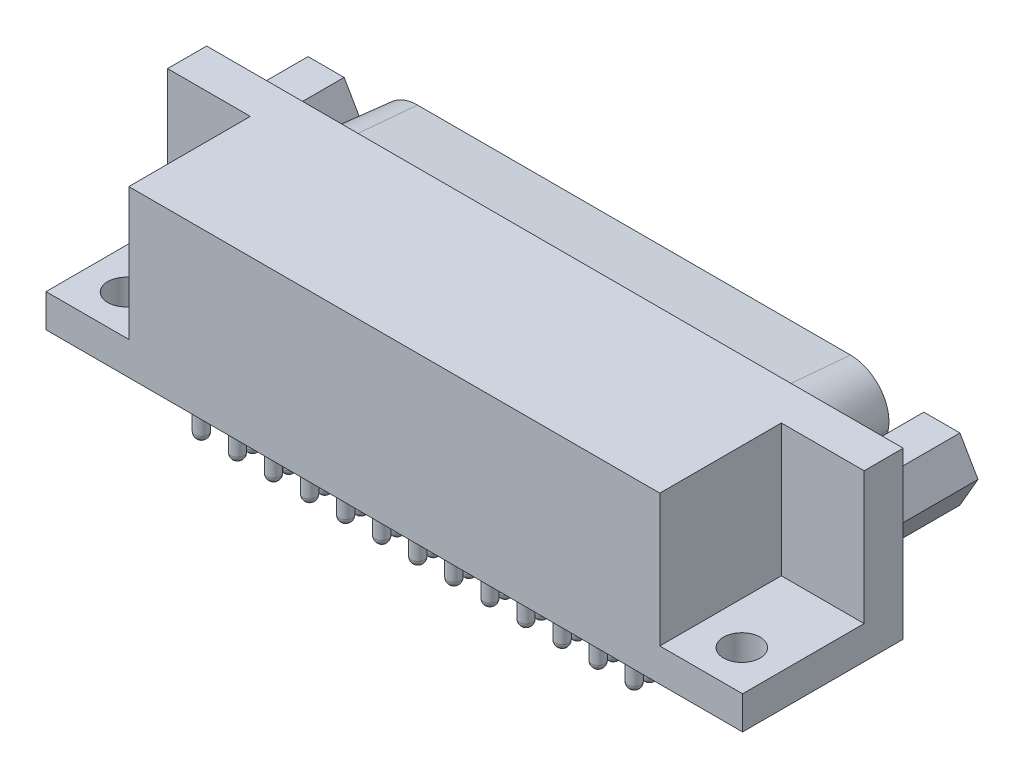
SolidWorks part; units mm, degrees
ref_plane "x/y" through (0, 0, 0) normal (0, 0, 1) x (1, 0, 0)
ref_plane "x/z" through (0, 0, 0) normal (0, 1, 0) x (1, 0, 0)
ref_plane "y/z" through (0, 0, 0) normal (1, 0, 0) x (0, 0, -1)
sketch "Sketch1" plane through (0, 0, 0) normal (0, 1, 0) x (1, 0, 0)
  line L1 (-10.16, -1.77) -> (43.31, -1.77)
  line L2 (-10.16, -1.77) -> (-10.16, 10.56)
  line L3 (-10.16, 10.56) -> (43.31, 10.56)
  line L4 (43.31, -1.77) -> (43.31, 10.56)
  point P3 (16.575, 10.56)
  dimension "D1" = 53.47
  dimension "D2" = 12.33
  dimension "D3" = 1.77
  dimension "D4" = 10.16
extrude "Base-Extrude" add sketch "Sketch1" along normal blind 12.7
sketch "Sketch2" plane through (0, 0, -10.56) normal (0, 0, -1) x (-1, 0, 0)
  line L0 (-16.575, 12.7) -> (-16.575, -6.5379) construction
  line L1 (-43.31, 12.7) -> (10.16, 12.7) construction
  line L2 (-32.6146, 1.37) -> (-0.5354, 1.37)
  line L3 (2.8812, 4.189) -> (3.4616, 7.189)
  line L4 (0.045, 11.33) -> (-33.195, 11.33)
  line L6 (-36.0312, 4.189) -> (-36.6116, 7.189)
  line L7 (-43.31, 0) -> (10.16, 0) construction
  arc A0 (2.8812, 4.189) -> (-0.5354, 1.37) centre (-0.5354, 4.85) cw
  arc A1 (0.045, 11.33) -> (3.4616, 7.189) centre (0.045, 7.85) cw
  arc A2 (-33.195, 11.33) -> (-36.6116, 7.189) centre (-33.195, 7.85) ccw
  arc A3 (-36.0312, 4.189) -> (-32.6146, 1.37) centre (-32.6146, 4.85) ccw
  point P4 (-16.575, 11.33)
  point P12 (2.3358, 1.37)
  point P21 (-16.575, 1.37)
  dimension "D5" = 3.48
  dimension "D1" = 1.37
  dimension "D2" = 1.37
  dimension "D3" = 100.95
  dimension "D4" = 33.24
extrude "Boss-Extrude1" add sketch "Sketch2" along normal blind 6.07 draft 5
sketch "Sketch13" plane through (0, 0, -16.63) normal (0, 0, -1) x (-1, 0, 0)
  line L8 (1.9671, 4.3658) -> (2.5475, 7.3658)
  line L9 (0.045, 10.3989) -> (-33.195, 10.3989)
  line L10 (-35.6975, 7.3658) -> (-35.1171, 4.3658)
  line L11 (-32.6146, 2.3011) -> (-0.5354, 2.3011)
  line L12 (1.9671, 4.3658) -> (2.5475, 7.3658)
  line L13 (0.045, 10.3989) -> (-33.195, 10.3989)
  line L14 (-35.6975, 7.3658) -> (-35.1171, 4.3658)
  line L15 (-32.6146, 2.3011) -> (-0.5354, 2.3011)
  arc A8 (-0.5354, 2.3011) -> (1.9671, 4.3658) centre (-0.5354, 4.85) ccw
  arc A9 (2.5475, 7.3658) -> (0.045, 10.3989) centre (0.045, 7.85) ccw
  arc A10 (-33.195, 10.3989) -> (-35.6975, 7.3658) centre (-33.195, 7.85) ccw
  arc A11 (-35.1171, 4.3658) -> (-32.6146, 2.3011) centre (-32.6146, 4.85) ccw
  arc A12 (-0.5354, 2.3011) -> (1.9671, 4.3658) centre (-0.5354, 4.85) ccw
  arc A13 (2.5475, 7.3658) -> (0.045, 10.3989) centre (0.045, 7.85) ccw
  arc A14 (-33.195, 10.3989) -> (-35.6975, 7.3658) centre (-33.195, 7.85) ccw
  arc A15 (-35.1171, 4.3658) -> (-32.6146, 2.3011) centre (-32.6146, 4.85) ccw
  dimension "D1" = 0.4
extrude "Cut-Extrude5" cut sketch "Sketch13" against normal up to vertex (6.07 mm away) draft 5 up to point (43.31, 12.7, -10.56) draft outward yes
sketch "Sketch6" plane through (0, 0, 0) normal (0, -1, 0) x (1, 0, 0)
  circle A0 centre (0, 0) radius 0.5
  dimension "D1" = 1
extrude "Boss-Extrude2" add sketch "Sketch6" along normal blind 2.54
dome "Dome3" faces to dome 1 distance 0.5 reverse direction no elliptical dome no face at (0, -2.54, -0.5) parameters "D1"=0.5
pattern_linear "LPattern1" count 13 spacing 2.7686 along (1, 0, 0) of "Dome3", "Boss-Extrude2"
sketch "Sketch7" plane through (0, 0, 0) normal (0, -1, 0) x (1, 0, 0)
  line L1 (-10.16, -10.56) -> (-10.16, 1.77) construction
  circle A0 centre (1.397, -2.54) radius 0.5
  circle A1 centre (0, 0) radius 0.5 construction
  dimension "D2" = 11.557
  dimension "D3" = 2.54
extrude "Boss-Extrude3" add sketch "Sketch7" along normal blind 4
dome "Dome4" faces to dome 1 distance 0.5 reverse direction no elliptical dome no face at (1.397, -4, -3.04) parameters "D1"=0.5
pattern_linear "LPattern4" count 12 spacing 2.7686 along (1, 0, 0) of "Boss-Extrude3", "Dome4"
sketch "Sketch14" plane through (0, 0, -10.56) normal (0, 0, -1) x (-1, 0, 0)
  circle A0 centre (0.045, 7.85) radius 0.5
  arc A1 (2.5475, 7.3658) -> (0.045, 10.3989) centre (0.045, 7.85) ccw construction
  dimension "D1" = 1
extrude "Boss-Extrude5" add sketch "Sketch14" along normal blind 4
dome "Dome1" faces to dome 1 distance 0.5 reverse direction no elliptical dome no face at (-0.545, 7.85, -14.56) parameters "D1"=0.5
pattern_linear "LPattern5" count 13 spacing 2.77 along (1, 0, 0) of "Dome1", "Boss-Extrude5"
sketch "Sketch15" plane through (0, 0, -10.56) normal (0, 0, -1) x (-1, 0, 0)
  line L1 (-2.725, 7.85) -> (0.045, 7.85) construction
  line L3 (-1.34, 7.85) -> (-1.34, 5.31) construction
  circle A0 centre (-1.34, 5.31) radius 0.5
  circle A1 centre (0.045, 7.85) radius 0.5 construction
  circle A2 centre (-2.725, 7.85) radius 0.5 construction
  dimension "D1" = 2.54
extrude "Boss-Extrude6" add sketch "Sketch15" along normal blind 4
dome "Dome2" faces to dome 1 distance 0.5 reverse direction no elliptical dome no face at (0.84, 5.31, -14.56) parameters "D1"=0.5
pattern_linear "LPattern6" count 12 spacing 2.77 along (1, 0, 0) of "Boss-Extrude6", "Dome2"
ref_plane "Plane1" through (16.575, 0, 0) normal (1, 0, 0) x (0, 0, -1)
sketch "Sketch12" plane through (0, 0, -10.56) normal (0, 0, -1) x (-1, 0, 0)
  line L0 (-43.31, 12.7) -> (10.16, 12.7) construction
  line L1 (-41.595, 9.82) -> (-42.98, 7.4211)
  line L2 (-42.98, 7.4211) -> (-41.595, 5.0222)
  line L3 (-41.595, 5.0222) -> (-38.825, 5.0222)
  line L4 (-38.825, 5.0222) -> (-37.44, 7.4211)
  line L5 (-37.44, 7.4211) -> (-38.825, 9.82)
  line L6 (-38.825, 9.82) -> (-41.595, 9.82)
  line L7 (-43.31, 12.7) -> (-43.31, 0) construction
  circle A0 centre (-40.21, 7.4211) radius 2.3989 construction
  circle A1 centre (-40.21, 7.4211) radius 1.3043
  dimension "D1" = 2.77
  dimension "D2" = 2.88
  dimension "D3" = 0.33
extrude "Boss-Extrude4" add sketch "Sketch12" along normal blind 6.07
sketch "Sketch9" plane through (0, 0, 1.77) normal (0, 0, 1) x (1, 0, 0)
  line L1 (-10.16, 12.7) -> (-3.8049, 12.7)
  line L2 (-10.16, 12.7) -> (-10.16, 2.54)
  line L3 (-10.16, 2.54) -> (-3.8049, 2.54)
  line L4 (-3.8049, 12.7) -> (-3.8049, 2.54)
  dimension "D1" = 10.16
  dimension "D2" = 6.3551
extrude "Cut-Extrude3" cut sketch "Sketch9" against normal blind 9.33
sketch "Sketch11" plane through (0, 2.54, 0) normal (0, 1, 0) x (-1, 0, 0)
  line L0 (10.16, 1.77) -> (3.8049, 1.77) construction
  line L1 (10.16, -7.56) -> (10.16, 1.77) construction
  circle A0 centre (7.06, -1.27) radius 1.4
  point P2 (6.9825, 1.77)
  dimension "D1" = 2.8
  dimension "D2" = 3.04
  dimension "D3" = 3.1
extrude "Cut-Extrude4" cut sketch "Sketch11" against normal through all
mirror "Mirror1" about plane through (16.575, 0, 0) normal (1, 0, 0) of "Boss-Extrude4", "Cut-Extrude3", "Cut-Extrude4"
